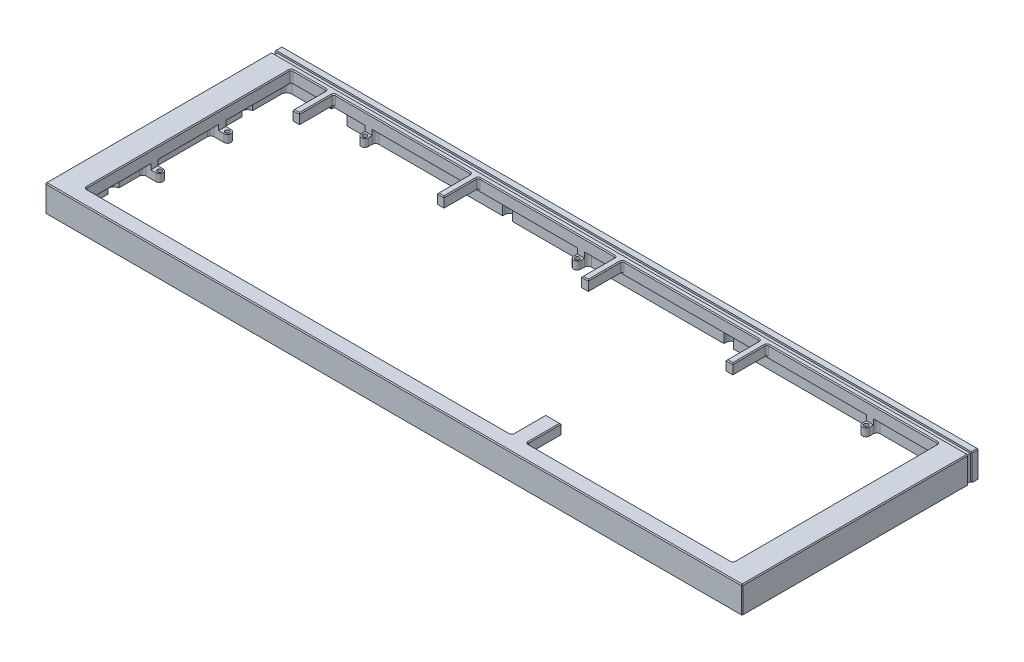
SolidWorks part; units mm, degrees
material "6061-T6 (SS)"
ref_plane "Front Plane" through (0, 0, 0) normal (0, 0, 1) x (1, 0, 0)
ref_plane "Top Plane" through (0, 0, 0) normal (0, 1, 0) x (1, 0, 0)
ref_plane "Right Plane" through (0, 0, 0) normal (1, 0, 0) x (0, 0, -1)
sketch "Sketch1" plane through (0, 0, 0) normal (0, 1, 0) x (1, 0, 0)
  line L1 (0, 0) -> (390.74, 0)
  line L2 (0, 0) -> (0, 132.7)
  line L3 (0, 132.7) -> (390.74, 132.7)
  line L4 (390.74, 0) -> (390.74, 132.7)
  line L5 (13.92, 124) -> (376.82, 124)
  line L6 (13.92, 124) -> (13.92, 8.7)
  line L7 (13.92, 8.7) -> (376.82, 8.7)
  line L8 (376.82, 124) -> (376.82, 8.7)
  point P9 (195.37, 124)
  point P10 (195.37, 132.7)
  point P11 (13.92, 66.35)
  point P12 (0, 66.35)
  dimension "D1" = 362.9
  dimension "D2" = 115.3
  dimension "D3" = 8.7
  dimension "D4" = 13.92
extrude "Main Body" add sketch "Sketch1" along normal blind 14.8
sketch "Sketch2" plane through (0, 0, 0) normal (0, -1, 0) x (1, 0, 0)
  line L0 (390.74, -132.7) -> (0, -132.7) construction
  line L1 (388.74, -130.7) -> (2, -130.7)
  line L2 (388.74, -130.7) -> (388.74, -2)
  line L3 (388.74, -2) -> (2, -2)
  line L4 (2, -130.7) -> (2, -2)
  line L5 (390.74, 0) -> (390.74, -132.7) construction
  point P4 (195.37, -130.7)
  point P7 (195.37, -132.7)
  point P8 (388.74, -66.35)
  point P11 (390.74, -66.35)
  dimension "D1" = 2
  dimension "D2" = 2
extrude "Alignment Guide" cut sketch "Sketch2" against normal blind 1 contours L2 L1 L4 L3
sketch "Sketch3" plane through (0, 14.8, 0) normal (0, 1, 0) x (1, 0, 0)
  line L0 (13.92, 8.7) -> (376.82, 8.7) construction
  line L1 (252.82, 27.8) -> (261.52, 27.8)
  line L2 (252.82, 27.8) -> (252.82, 8.7)
  line L3 (252.82, 8.7) -> (261.52, 8.7)
  line L4 (261.52, 27.8) -> (261.52, 8.7)
  line L5 (376.82, 8.7) -> (376.82, 124) construction
  line L6 (376.82, 124) -> (13.92, 124) construction
  line L7 (33.92, 124) -> (37.72, 124)
  line L8 (33.92, 124) -> (33.92, 104.9)
  line L9 (33.92, 104.9) -> (37.72, 104.9)
  line L10 (37.72, 124) -> (37.72, 104.9)
  line L11 (13.92, 124) -> (13.92, 8.7) construction
  line L12 (114.92, 124) -> (118.72, 124)
  line L13 (114.92, 124) -> (114.92, 104.9)
  line L14 (114.92, 104.9) -> (118.72, 104.9)
  line L15 (118.72, 124) -> (118.72, 104.9)
  line L16 (195.82, 124) -> (199.62, 124)
  line L17 (195.82, 124) -> (195.82, 104.9)
  line L18 (195.82, 104.9) -> (199.62, 104.9)
  line L19 (199.62, 124) -> (199.62, 104.9)
  line L20 (276.82, 124) -> (280.62, 124)
  line L21 (276.82, 124) -> (276.82, 104.9)
  line L22 (276.82, 104.9) -> (280.62, 104.9)
  line L23 (280.62, 124) -> (280.62, 104.9)
  point P8 (257.17, 8.7)
  dimension "D1" = 115.3
  dimension "D2" = 124
  dimension "D3" = 19.1
  dimension "D4" = 3.8
  dimension "D5" = 19.1
  dimension "D6" = 77.2
  dimension "D7" = 77.1
  dimension "D8" = 77.2
  dimension "D9" = 20
extrude "Blockers" add sketch "Sketch3" against normal blind 5.5
fillet "Fillet5" radius 1 14 edges at (280.62, 12.05, -124) (276.82, 12.05, -124) (195.82, 12.05, -124) (199.62, 12.05, -124) (118.72, 12.05, -124) (114.92, 12.05, -124) (33.92, 12.05, -124) (37.72, 12.05, -124) (13.92, 7.9, -124) (13.92, 7.9, -8.7) (252.82, 12.05, -8.7) (261.52, 12.05, -8.7) (376.82, 7.9, -8.7) (376.82, 7.9, -124)
sketch "Sketch4" plane through (0, 1, 0) normal (0, -1, 0) x (1, 0, 0)
  line L0 (0, 0) -> (390.74, 0) construction
  line L1 (381.27, -125.9) -> (9.47, -125.9)
  line L2 (381.27, -125.9) -> (381.27, -6.8)
  line L3 (381.27, -6.8) -> (9.47, -6.8)
  line L4 (9.47, -125.9) -> (9.47, -6.8)
  line L5 (390.74, 0) -> (390.74, -132.7) construction
  point P4 (195.37, -6.8)
  point P7 (195.37, 0)
  point P8 (381.27, -66.35)
  point P11 (390.74, -66.35)
  dimension "D1" = 119.1
  dimension "D2" = 371.8
extrude "PCB Cutout" cut sketch "Sketch4" against normal offset from surface (7.3 mm away) 6.5 up to face at (195.37, 14.8, -66.35)
fillet "Fillet4" radius 3 8 edges at (9.47, 4.65, -6.8) (9.47, 4.65, -125.9) (381.27, 4.65, -125.9) (381.27, 4.65, -6.8) (2, 0.5, -130.7) (2, 0.5, -2) (388.74, 0.5, -2) (388.74, 0.5, -130.7)
sketch "Sketch6" plane through (0, 1, 0) normal (0, -1, 0) x (1, 0, 0)
  line L0 (381.27, -9.8) -> (381.27, -122.9) construction
  line L1 (254.62, -127.1) -> (260.12, -127.1)
  line L2 (254.62, -127.1) -> (254.62, -125.9)
  line L3 (254.62, -125.9) -> (260.12, -125.9)
  line L4 (260.12, -127.1) -> (260.12, -125.9)
  line L5 (12.47, -125.9) -> (378.27, -125.9) construction
  line L11 (378.27, -6.8) -> (12.47, -6.8) construction
  line L16 (260.12, -6.8) -> (254.62, -6.8)
  line L17 (260.12, -6.8) -> (260.12, -4.8)
  line L18 (260.12, -4.8) -> (254.62, -4.8)
  line L19 (254.62, -6.8) -> (254.62, -4.8)
  line L21 (0, 0) -> (390.74, 0) construction
  line L24 (390.74, -66.35) -> (195.37, -66.35) construction
  line L25 (390.74, 0) -> (390.74, -132.7) construction
  line L26 (328.6755, -66.35) -> (328.6755, -130.7) construction
  line L27 (385.74, -130.7) -> (5, -130.7) construction
  line L28 (328.6755, -66.35) -> (328.6755, -8.7) construction
  line L29 (375.82, -8.7) -> (14.92, -8.7) construction
  line L55 (390.74, -132.7) -> (0, -132.7) construction
  line L56 (195.37, -132.7) -> (195.37, 0) construction
  line L57 (136.12, -6.8) -> (136.12, -4.8)
  line L58 (130.62, -4.8) -> (136.12, -4.8)
  line L59 (130.62, -6.8) -> (130.62, -4.8)
  line L60 (130.62, -6.8) -> (136.12, -6.8)
  line L61 (130.62, -127.1) -> (130.62, -125.9)
  line L62 (136.12, -125.9) -> (130.62, -125.9)
  line L63 (136.12, -127.1) -> (136.12, -125.9)
  line L64 (136.12, -127.1) -> (130.62, -127.1)
  circle A0 centre (381.07, -103.85) radius 3
  circle A1 centre (381.07, -28.85) radius 3
  circle A2 centre (257.37, -4.8) radius 2.75
  circle A3 centre (257.37, -127.1) radius 2.75
  circle A8 centre (133.37, -4.8) radius 2.75
  circle A9 centre (9.67, -28.85) radius 3
  circle A10 centre (9.67, -103.85) radius 3
  circle A11 centre (133.37, -127.1) radius 2.75
  point P25 (195.37, -66.35)
  point P32 (257.37, -125.9)
  point P33 (257.37, -6.8)
  line M17 (12.47, -6.8) -> (378.27, -6.8)
  line M18 (381.27, -9.8) -> (381.27, -122.9)
  line M19 (378.27, -125.9) -> (12.47, -125.9)
  line M20 (9.47, -122.9) -> (9.47, -9.8)
  dimension "D4" = 6
  dimension "D5" = 62
  dimension "D8" = 5.5
  dimension "D1" = 37.5
  dimension "D2" = 4.8
  dimension "D3" = 37.5
  dimension "D6" = 0.2
  dimension "D7" = 5.6
extrude "PlateTabs" cut sketch "Sketch6" against normal up to surface (7.3 mm away) contours A0 M18 | A1 M18 | A2 L19 M17 | L16 A2 L18 | A2 L17 M17 | L18 A2 | L1 A3 | L1 A3 L3 | A3 L2 M19 | A11 L64 | A11 L64 L62 | A10 M20 | A9 M20 | A8 L58 | A8 L60 L58 | A3 L4 M19 | A8 L59 M17 | L57 A8 M17 | A11 L63 M19 | L61 A11 M19 | A11 | L59 L58 L57 L60 | A3 region at (257.37, 1, -126.5102) region at (136.0381, 1, -126.1969) region at (257.37, 1, -128.2671) region at (254.7019, 1, -126.1969) region at (260.0381, 1, -126.1969) region at (133.37, 1, -126.5102) region at (133.37, 1, -128.2671) region at (130.7019, 1, -126.1969) region at (135.8701, 1, -6.317) region at (259.8701, 1, -6.317) region at (257.37, 1, -5.7445) region at (257.37, 1, -3.6329) region at (254.8699, 1, -6.317) region at (133.37, 1, -5.7445) region at (133.37, 1, -3.6329) region at (130.8699, 1, -6.317) region at (382.452, 1, -103.85) region at (382.452, 1, -28.85) region at (8.288, 1, -103.85) region at (8.288, 1, -28.85) up to face at (195.37, 8.3, -66.35)
sketch "Sketch9" plane through (0, 0, -132.7) normal (0, 0, -1) x (-1, 0, 0)
  line L1 (-41.8, 0) -> (-29.8, 0)
  line L2 (-41.8, 0) -> (-41.8, 3.2)
  line L3 (-41.8, 3.2) -> (-29.8, 3.2)
  line L4 (-29.8, 0) -> (-29.8, 3.2)
  line L5 (-390.74, 0) -> (0, 0) construction
  line L7 (0, 14.8) -> (0, 0) construction
  point P6 (-35.8, 3.2)
  dimension "D1" = 3.2
  dimension "D3" = 12
  dimension "D4" = 35.8
extrude "USB Cutout" cut sketch "Sketch9" against normal up to surface (8.7 mm away) up to face at (164.89, 11.95, -124)
sketch "Sketch11" plane through (0, 0, -125.9) normal (0, 0, 1) x (1, 0, 0)
  line L0 (130.62, 8.3) -> (12.47, 8.3) construction
  line L1 (43.3, 1) -> (28.3, 1)
  line L2 (43.3, 1) -> (43.3, 8.3)
  line L3 (43.3, 8.3) -> (28.3, 8.3)
  line L4 (28.3, 1) -> (28.3, 8.3)
  line L7 (12.47, 1) -> (29.8, 1) construction
  line L8 (29.8, 3.2) -> (41.8, 3.2) construction
  point P8 (35.8, 1)
  point P18 (35.8, 3.2)
  dimension "D1" = 15
extrude "PCB Clearance" cut sketch "Sketch11" against normal blind 3.9
fillet "Fillet7" radius 2.5 2 edges at (28.3, 4.65, -129.8) (43.3, 4.65, -129.8)
sketch "Sketch12" plane through (0, 8.3, 0) normal (0, -1, 0) x (1, 0, 0)
  line L0 (195.37, -132.7) -> (195.37, 0) construction
  line L2 (14.92, -124) -> (375.82, -124) construction
  line L3 (0, 0) -> (390.74, 0) construction
  line L5 (390.74, -132.7) -> (41.8, -132.7) construction
  line L8 (376.82, -123) -> (376.82, -9.7) construction
  arc A0 (381.27, -31.8433) -> (381.27, -25.8567) centre (381.07, -28.85) ccw construction
  arc A1 (381.27, -106.8433) -> (381.27, -100.8567) centre (381.07, -103.85) ccw construction
  point P0 (257.37, -127.1)
  point P1 (381.42, -103.85)
  point P2 (381.42, -28.85)
  point P3 (257.37, -4.85)
  point P7 (195.37, -66.35)
  point P8 (133.37, -4.85)
  point P10 (9.32, -28.85)
  point P14 (9.32, -103.85)
  point P16 (133.37, -127.1)
  point P34 (384.07, -28.85)
  point P39 (384.07, -103.85)
  dimension "D1" = 3.1
  dimension "D2" = 61.5
  dimension "D3" = 4.6
  dimension "D4" = 62
chamfer "Chamfer1" distance 0.5 46 edges at (14.2129, 14.8, -8.9929) (133.37, 14.8, -8.7) (252.5271, 14.8, -8.9929) (252.82, 14.8, -18.75) (257.17, 14.8, -27.8) (261.52, 14.8, -18.75) (261.8129, 14.8, -8.9929) (319.17, 14.8, -8.7) (376.5271, 14.8, -8.9929) (376.82, 14.8, -66.35) (376.5271, 14.8, -123.7071) (328.72, 14.8, -124) (280.9129, 14.8, -123.7071) (280.62, 14.8, -113.95) (278.72, 14.8, -104.9) (276.82, 14.8, -113.95) (276.5271, 14.8, -123.7071) (238.22, 14.8, -124) (199.9129, 14.8, -123.7071) (199.62, 14.8, -113.95) (197.72, 14.8, -104.9) (195.82, 14.8, -113.95) (195.5271, 14.8, -123.7071) (157.27, 14.8, -124) (119.0129, 14.8, -123.7071) (118.72, 14.8, -113.95) (116.82, 14.8, -104.9) (114.92, 14.8, -113.95) (114.6271, 14.8, -123.7071) (76.32, 14.8, -124) (38.0129, 14.8, -123.7071) (37.72, 14.8, -113.95) (35.82, 14.8, -104.9) (33.92, 14.8, -113.95) (33.6271, 14.8, -123.7071) (23.92, 14.8, -124) (14.2129, 14.8, -123.7071) (13.92, 14.8, -66.35) (195.37, 14.8, -132.7) (390.74, 14.8, -66.35) (195.37, 14.8, 0) (0, 14.8, -66.35) (390.74, 7.4, -132.7) (390.74, 7.4, 0) (0, 7.4, -132.7) (0, 7.4, 0)
chamfer "Chamfer2" distance 0.1 5 edges at (390.74, 0, -66.35) (195.37, 0, 0) (0, 0, -66.35) (15.15, 0, -132.7) (216.02, 0, -132.7)
sketch "Sketch27" plane through (0, 14.8, 0) normal (0, 1, 0) x (1, 0, 0)
  line L0 (0, 0.5) -> (0, 132.2) construction
  line L1 (0, 128.95) -> (390.74, 128.95)
  line L2 (0, 128.95) -> (0, 126.45)
  line L3 (0, 126.45) -> (390.74, 126.45)
  line L4 (390.74, 128.95) -> (390.74, 126.45)
  line L5 (390.74, 132.2) -> (390.74, 0.5) construction
  line L6 (372.9261, 132.2) -> (372.9261, 124.5) construction
  line L7 (390.24, 132.2) -> (0.5, 132.2) construction
  line L9 (281.62, 124.5) -> (375.82, 124.5) construction
  point P14 (390.74, 127.7)
  dimension "D1" = 2.5
  dimension "D2" = 3.2
extrude "Cut-Extrude11" cut sketch "Sketch27" against normal blind 1
sketch "Sketch28" plane through (0, 13.8, 0) normal (0, 1, 0) x (1, 0, 0)
  line L1 (0, 128.95) -> (1, 128.95)
  line L2 (0, 128.95) -> (0, 126.45)
  line L3 (0, 126.45) -> (1, 126.45)
  line L4 (1, 128.95) -> (1, 126.45)
  line L5 (389.74, 128.95) -> (390.74, 128.95)
  line L6 (389.74, 128.95) -> (389.74, 126.45)
  line L7 (389.74, 126.45) -> (390.74, 126.45)
  line L8 (390.74, 128.95) -> (390.74, 126.45)
  line L9 (390.74, 128.95) -> (0, 128.95) construction
  line L10 (0, 126.45) -> (390.74, 126.45) construction
  dimension "D1" = 1
  dimension "D2" = 1
extrude "Cut-Extrude12" cut sketch "Sketch28" against normal through all
sketch "Sketch21" [suppressed] plane through (0, 14.8, 0) normal (0, 1, 0) x (1, 0, 0)
  line L0 (0.5, 132.7) -> (390.24, 132.7) construction
  line L1 (382.53, 132.7) -> (385.03, 132.7)
  line L2 (382.53, 132.7) -> (382.53, 72.7)
  line L3 (382.53, 72.7) -> (385.03, 72.7)
  line L4 (385.03, 132.7) -> (385.03, 72.7)
  line L5 (390.74, 132.2) -> (390.74, 129.7) construction
  line L6 (390.74, 129.1) -> (294.74, 129.1)
  line L7 (390.74, 129.1) -> (390.74, 127.6)
  line L8 (390.74, 127.6) -> (294.74, 127.6)
  line L9 (294.74, 129.1) -> (294.74, 127.6)
  line L10 (362.9081, 132.2) -> (362.9081, 124.5) construction
  line L11 (390.24, 132.2) -> (0.5, 132.2) construction
  line L12 (281.62, 124.5) -> (375.82, 124.5) construction
  line L13 (365.5702, 129.1) -> (365.5702, 127.6) construction
  line L14 (377.32, 119.5259) -> (390.24, 119.5259) construction
  line L15 (377.32, 123) -> (377.32, 9.7) construction
  line L16 (390.24, 0.5) -> (390.24, 127.2) construction
  line L17 (382.53, 116.0504) -> (385.03, 116.0504) construction
  point P28 (383.78, 116.0504)
  point P29 (383.78, 119.5259)
  point P30 (365.5702, 128.35)
  point P31 (362.9081, 128.35)
  dimension "D1" = 2.5
  dimension "D2" = 1.5
  dimension "D3" = 60
  dimension "D4" = 96
extrude "Cut-Extrude5" [suppressed] cut sketch "Sketch21" against normal blind 1 contours L4 L3 L2 L1 | L8 L9 L6 L7
sketch "Sketch23" [suppressed] plane through (390.74, 0, 0) normal (1, 0, 0) x (0, 0, -1)
  line L0 (129.1, 13.8) -> (129.1, 14.3) construction
  line L1 (127.6, 13.8) -> (129.1, 13.8)
  line L2 (127.6, 13.8) -> (127.6, 0)
  line L3 (127.6, 0) -> (129.1, 0)
  line L4 (129.1, 13.8) -> (129.1, 0)
extrude "Cut-Extrude6" [suppressed] cut sketch "Sketch23" against normal blind 1
sketch "Sketch19" plane through (0, 14.8, 0) normal (0, 1, 0) x (1, 0, 0)
  line L0 (0.5, 132.7) -> (390.24, 132.7) construction
  line L1 (5.46, 132.7) -> (8.46, 132.7)
  line L2 (5.46, 132.7) -> (5.46, 0)
  line L3 (5.46, 0) -> (8.46, 0)
  line L4 (8.46, 132.7) -> (8.46, 0)
  line L7 (382.28, 132.7) -> (385.28, 132.7)
  line L8 (382.28, 132.7) -> (382.28, 0)
  line L9 (382.28, 0) -> (385.28, 0)
  line L10 (385.28, 132.7) -> (385.28, 0)
  line L11 (390.24, 0) -> (0.5, 0) construction
  line L12 (377.32, 110.209) -> (390.24, 110.209) construction
  line L13 (377.32, 123) -> (377.32, 9.7) construction
  line L14 (390.24, 0.5) -> (390.24, 126.45) construction
  line L15 (382.28, 106.8719) -> (385.28, 106.8719) construction
  line L16 (0.5, 106.8719) -> (13.42, 106.8719) construction
  line L17 (0.5, 132.2) -> (0.5, 128.95) construction
  line L18 (13.42, 9.7) -> (13.42, 123) construction
  line L19 (5.46, 102.7297) -> (8.46, 102.7297) construction
  point P12 (383.78, 106.8719)
  point P14 (383.78, 110.209)
  point P30 (6.96, 102.7297)
  point P31 (6.96, 106.8719)
  dimension "D1" = 3
  dimension "D2" = 3
extrude "Cut-Extrude3" [suppressed] cut sketch "Sketch19" against normal blind 1
sketch "Sketch17" plane through (0, 14.8, 0) normal (0, 1, 0) x (1, 0, 0)
  line L0 (390.24, 0.5) -> (390.24, 126.45) construction
  line L1 (5.71, 129.6) -> (385.03, 129.6)
  line L2 (5.71, 129.6) -> (5.71, -2.65)
  line L3 (5.71, -2.65) -> (385.03, -2.65)
  line L4 (385.03, 129.6) -> (385.03, -2.65)
  line L5 (8.21, 127.1) -> (382.53, 127.1)
  line L6 (8.21, 127.1) -> (8.21, -0.15)
  line L7 (8.21, -0.15) -> (382.53, -0.15)
  line L8 (382.53, 127.1) -> (382.53, -0.15)
  line L9 (390.24, 132.2) -> (0.5, 132.2) construction
  line L10 (21.2533, 132.2) -> (21.2533, 124.5) construction
  line L11 (14.92, 124.5) -> (32.92, 124.5) construction
  line L12 (25.2757, 129.6) -> (25.2757, 127.1) construction
  line L13 (0.5, 116.1326) -> (13.42, 116.1326) construction
  line L14 (0.5, 132.2) -> (0.5, 128.95) construction
  line L15 (13.42, 9.7) -> (13.42, 123) construction
  line L16 (5.71, 120.1548) -> (8.21, 120.1548) construction
  point P8 (382.53, 63.475)
  point P9 (385.03, 63.475)
  point P12 (390.24, 63.475)
  point P13 (195.37, 129.6)
  point P14 (195.37, 127.1)
  point P17 (195.37, 132.2)
  point P24 (25.2757, 128.35)
  point P25 (21.2533, 128.35)
  point P34 (6.96, 116.1326)
  point P35 (6.96, 120.1548)
  dimension "D1" = 2.5
  dimension "D2" = 2.5
extrude "Cut-Extrude1" [suppressed] cut sketch "Sketch17" against normal blind 1
hole_wizard "M2x0.4 Tapped Hole1" positions "3DSketch3" profile "Sketch31" tap size "M2x0.4" standard "ANSI Metric"
sketch3d "3DSketch3"
  point P0 (381.42, 8.3, -103.85)
  point P3 (381.42, 8.3, -28.85)
  point P7 (257.37, 8.3, -4.85)
  point P10 (133.37, 8.3, -4.85)
  point P13 (9.32, 8.3, -28.85)
  point P16 (9.32, 8.3, -103.85)
  point P19 (133.37, 8.3, -127.1)
  point P22 (257.37, 8.3, -127.1)
sketch "Sketch31" plane through (381.42, 8.3, -103.85) normal (1, 0, 0) x (0, 0, -1)
  line L0 (0, 0) -> (0, 4.4807)
  line L1 (0, 4.4807) -> (0.8, 4)
  line L2 (0.8, 4) -> (0.8, 0)
  line L5 (0.8, 0) -> (0, 0)
  line L10 (0, 4.4807) -> (-0.8, 4) construction
  line L11 (0, -6.35) -> (0, 107.95) construction
  dimension "Tap Drill Dia." = 1.6
  dimension "Tap Drill Depth" = 4
  dimension "Drill Angle" = 118
cosmetic thread "Hole Thread19" parameters "D1"=4, "D2"=2
cosmetic thread "Hole Thread20" parameters "D1"=4, "D2"=2
cosmetic thread "Hole Thread21" parameters "D1"=4, "D2"=2
cosmetic thread "Hole Thread22" parameters "D1"=4, "D2"=2
cosmetic thread "Hole Thread23" parameters "D1"=4, "D2"=2
cosmetic thread "Hole Thread24" parameters "D1"=4, "D2"=2
cosmetic thread "Hole Thread25" parameters "D1"=4, "D2"=2
cosmetic thread "Hole Thread26" parameters "D1"=4, "D2"=2
fillet "Fillet8" radius 0.1 9 edges at (213.77, 0, -130.7) (387.8613, 0, -129.8213) (17.4, 0, -130.7) (2.8787, 0, -129.8213) (2, 0, -66.35) (2.8787, 0, -2.8787) (195.37, 0, -2) (387.8613, 0, -2.8787) (388.74, 0, -66.35)
sketch "Sketch32" plane through (0, 1, 0) normal (0, -1, 0) x (1, 0, 0)
  line L1 (0, -126.45) -> (0, -0.5) construction
  line L3 (378.27, -125.9) -> (260.12, -125.9) construction
  line L4 (340.3, -121.9) -> (336.3, -121.9)
  line L5 (340.3, -121.9) -> (340.3, -125.9)
  line L6 (340.3, -125.9) -> (336.3, -125.9)
  line L7 (336.3, -121.9) -> (336.3, -125.9)
  line L8 (254.62, -125.9) -> (136.12, -125.9) construction
  line L9 (178.4, -121.9) -> (174.4, -121.9)
  line L10 (178.4, -121.9) -> (178.4, -125.9)
  line L11 (178.4, -125.9) -> (174.4, -125.9)
  line L12 (174.4, -121.9) -> (174.4, -125.9)
  line L13 (43.3, -125.9) -> (130.62, -125.9) construction
  line L14 (59.3, -121.9) -> (55.3, -121.9)
  line L15 (59.3, -121.9) -> (59.3, -125.9)
  line L16 (59.3, -125.9) -> (55.3, -125.9)
  line L17 (55.3, -121.9) -> (55.3, -125.9)
  line L18 (9.47, -31.8433) -> (9.47, -100.8567) construction
  line L19 (16.8, -83.4) -> (9.47, -83.4)
  line L20 (16.8, -83.4) -> (16.8, -87.4)
  line L21 (16.8, -87.4) -> (9.47, -87.4)
  line L22 (9.47, -83.4) -> (9.47, -87.4)
  line L23 (12.47, -6.8) -> (130.62, -6.8) construction
  line L24 (16.8, -45.3) -> (9.47, -45.3)
  line L25 (16.8, -45.3) -> (16.8, -49.3)
  line L26 (16.8, -49.3) -> (9.47, -49.3)
  line L27 (9.47, -45.3) -> (9.47, -49.3)
  line L28 (87.9, -11.6) -> (83.9, -11.6)
  line L29 (87.9, -11.6) -> (87.9, -6.8)
  line L30 (87.9, -6.8) -> (83.9, -6.8)
  line L31 (83.9, -11.6) -> (83.9, -6.8)
  line L32 (254.62, -6.8) -> (136.12, -6.8) construction
  line L33 (158.5, -11.6) -> (154.5, -11.6)
  line L34 (158.5, -11.6) -> (158.5, -6.8)
  line L35 (158.5, -6.8) -> (154.5, -6.8)
  line L36 (154.5, -11.6) -> (154.5, -6.8)
  line L37 (378.27, -6.8) -> (260.12, -6.8) construction
  line L38 (302.2, -11.6) -> (298.2, -11.6)
  line L39 (302.2, -11.6) -> (302.2, -6.8)
  line L40 (302.2, -6.8) -> (298.2, -6.8)
  line L41 (298.2, -11.6) -> (298.2, -6.8)
  line L42 (195.37, 0) -> (195.37, -132.6) construction
  line L43 (0.5, 0) -> (390.24, 0) construction
  line L44 (381.27, -45.3) -> (381.27, -49.3)
  line L45 (373.94, -49.3) -> (381.27, -49.3)
  line L46 (373.94, -45.3) -> (373.94, -49.3)
  line L47 (373.94, -45.3) -> (381.27, -45.3)
  line L48 (381.27, -83.4) -> (381.27, -87.4)
  line L49 (373.94, -87.4) -> (381.27, -87.4)
  line L50 (373.94, -83.4) -> (373.94, -87.4)
  line L51 (373.94, -83.4) -> (381.27, -83.4)
  line L52 (41.8, -132.6) -> (390.34, -132.6) construction
  line L53 (29.8, -132.7) -> (41.8, -132.7) construction
  circle A0 centre (338.3, -121.9) radius 2
  circle A1 centre (176.4, -121.9) radius 2
  circle A2 centre (57.3, -121.9) radius 2
  circle A3 centre (16.8, -85.4) radius 2
  circle A4 centre (16.8, -47.3) radius 2
  circle A5 centre (85.9, -11.6) radius 2
  circle A6 centre (156.5, -11.6) radius 2
  circle A7 centre (300.2, -11.6) radius 2
  circle A8 centre (373.94, -47.3) radius 2
  circle A9 centre (373.94, -85.4) radius 2
  dimension "D1" = 4
  dimension "D2" = 10.8
  dimension "D3" = 57.3
  dimension "D4" = 119.1
  dimension "D5" = 161.9
  dimension "D6" = 36.5
  dimension "D7" = 38.1
  dimension "D8" = 28.6
  dimension "D9" = 70.6
  dimension "D10" = 143.7
  dimension "D11" = 40.5
  dimension "D12" = 110.3
extrude "Boss-Extrude1" add sketch "Sketch32" against normal offset from surface (4.3 mm away) 3 contours A1 | L12 L11 L10 L9 | A0 | L5 L6 L7 L4 | A9 | L51 L48 L49 L50 | L47 L44 L45 L46 | A8 | L41 L40 L39 L38 | A7 | A6 | L36 L35 L34 L33 | A5 | L31 L30 L29 L28 | A4 | L26 L27 L24 L25 | A3 | L19 L22 L21 L20 | A2 | L15 L16 L17 L14 up to face at (381.42, 8.3, -104.65)
sketch "Sketch33" plane through (0, 8.3, 0) normal (0, -1, 0) x (1, 0, 0)
  line L0 (373.94, -83.4) -> (381.27, -83.4) construction
  line L1 (381.27, -87.4) -> (376.82, -87.4)
  line L2 (381.27, -87.4) -> (381.27, -83.4)
  line L3 (381.27, -83.4) -> (376.82, -83.4)
  line L4 (376.82, -87.4) -> (376.82, -83.4)
  line L5 (376.82, -123) -> (376.82, -9.7) construction
  line L6 (373.94, -45.3) -> (381.27, -45.3) construction
  line L7 (381.27, -49.3) -> (376.82, -49.3)
  line L8 (381.27, -49.3) -> (381.27, -45.3)
  line L9 (381.27, -45.3) -> (376.82, -45.3)
  line L10 (376.82, -49.3) -> (376.82, -45.3)
  line L11 (375.82, -8.7) -> (14.92, -8.7) construction
  line L12 (302.2, -6.8) -> (298.2, -6.8)
  line L13 (302.2, -6.8) -> (302.2, -8.7)
  line L14 (302.2, -8.7) -> (298.2, -8.7)
  line L15 (298.2, -6.8) -> (298.2, -8.7)
  line L16 (298.2, -11.6) -> (298.2, -6.8) construction
  line L17 (154.5, -11.6) -> (154.5, -6.8) construction
  line L18 (158.5, -6.8) -> (154.5, -6.8)
  line L19 (158.5, -6.8) -> (158.5, -8.7)
  line L20 (158.5, -8.7) -> (154.5, -8.7)
  line L21 (154.5, -6.8) -> (154.5, -8.7)
  line L22 (83.9, -11.6) -> (83.9, -6.8) construction
  line L23 (87.9, -6.8) -> (83.9, -6.8)
  line L24 (87.9, -6.8) -> (87.9, -8.7)
  line L25 (87.9, -8.7) -> (83.9, -8.7)
  line L26 (83.9, -6.8) -> (83.9, -8.7)
  line L27 (16.8, -49.3) -> (9.47, -49.3) construction
  line L28 (9.47, -45.3) -> (13.92, -45.3)
  line L29 (9.47, -45.3) -> (9.47, -49.3)
  line L30 (9.47, -49.3) -> (13.92, -49.3)
  line L31 (13.92, -45.3) -> (13.92, -49.3)
  line L32 (13.92, -9.7) -> (13.92, -123) construction
  line L33 (16.8, -87.4) -> (9.47, -87.4) construction
  line L34 (9.47, -83.4) -> (13.92, -83.4)
  line L35 (9.47, -83.4) -> (9.47, -87.4)
  line L36 (9.47, -87.4) -> (13.92, -87.4)
  line L37 (13.92, -83.4) -> (13.92, -87.4)
  line L38 (59.3, -121.9) -> (59.3, -125.9) construction
  line L39 (55.3, -125.9) -> (59.3, -125.9)
  line L40 (55.3, -125.9) -> (55.3, -124)
  line L41 (55.3, -124) -> (59.3, -124)
  line L42 (59.3, -125.9) -> (59.3, -124)
  line L43 (14.92, -124) -> (375.82, -124) construction
  line L44 (178.4, -121.9) -> (178.4, -125.9) construction
  line L45 (174.4, -125.9) -> (178.4, -125.9)
  line L46 (174.4, -125.9) -> (174.4, -124)
  line L47 (174.4, -124) -> (178.4, -124)
  line L48 (178.4, -125.9) -> (178.4, -124)
  line L49 (340.3, -121.9) -> (340.3, -125.9) construction
  line L50 (336.3, -125.9) -> (340.3, -125.9)
  line L51 (336.3, -125.9) -> (336.3, -124)
  line L52 (336.3, -124) -> (340.3, -124)
  line L53 (340.3, -125.9) -> (340.3, -124)
extrude "Boss-Extrude2" add sketch "Sketch33" along normal up to surface (3 mm away) up to face at (338.3, 5.3, -123.4)
fillet "Fillet9" radius 1.9 19 edges at (340.3, 4.65, -125.9) (336.3, 4.65, -125.9) (174.4, 4.65, -125.9) (178.4, 4.65, -125.9) (59.3, 4.65, -125.9) (55.3, 4.65, -125.9) (9.47, 4.65, -87.4) (9.47, 4.65, -83.4) (9.47, 4.65, -45.3) (9.47, 4.65, -49.3) (87.9, 4.65, -6.8) (83.9, 4.65, -6.8) (154.5, 4.65, -6.8) (158.5, 4.65, -6.8) (302.2, 4.65, -6.8) (298.2, 4.65, -6.8) (381.27, 4.65, -45.3) (381.27, 4.65, -49.3) (381.27, 4.65, -87.4)
sketch "Sketch34" plane through (0, 5.3, 0) normal (0, 1, 0) x (1, 0, 0)
  point P0 (16.8, 47.3)
  point P1 (16.8, 85.4)
  point P3 (85.9, 11.6)
  point P5 (156.5, 11.6)
  point P7 (300.2, 11.6)
  point P9 (373.94, 47.3)
  point P11 (373.94, 85.4)
  point P13 (338.3, 121.9)
  point P15 (176.4, 121.9)
  point P17 (57.3, 121.9)
hole_wizard "M2 Clearance Hole1" positions "3DSketch4" profile "Sketch35" hole size "M2" standard "ANSI Metric" end condition through all
sketch3d "3DSketch4"
  point P0 (57.3, 5.3, -121.9)
  point P3 (16.8, 5.3, -85.4)
  point P6 (16.8, 5.3, -47.3)
  point P9 (85.9, 5.3, -11.6)
  point P12 (156.5, 5.3, -11.6)
  point P15 (300.2, 5.3, -11.6)
  point P18 (373.94, 5.3, -47.3)
  point P21 (373.94, 5.3, -85.4)
  point P24 (338.3, 5.3, -121.9)
  point P27 (176.4, 5.3, -121.9)
sketch "Sketch35" plane through (57.3, 5.3, -121.9) normal (1, 0, 0) x (0, 0, 1)
  line L0 (0, 0) -> (0, 5.3)
  line L1 (0, 5.3) -> (1.2, 5.3)
  line L2 (1.2, 5.3) -> (1.2, 0)
  line L5 (1.2, 0) -> (0, 0)
  line L11 (0, -6.35) -> (0, 107.95) construction
  dimension "Thru Hole Dia." = 2.4
  dimension "Thru Hole Depth" = 5.3
